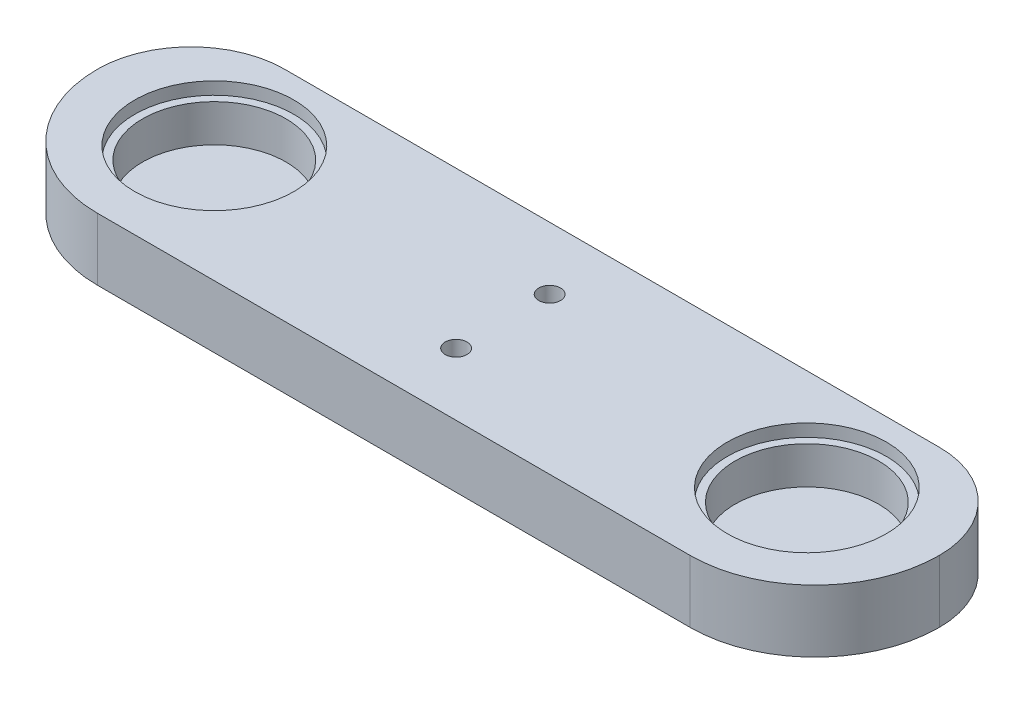
SolidWorks part; units mm, degrees
ref_plane "Front Plane" through (0, 0, 0) normal (0, 0, 1) x (1, 0, 0)
ref_plane "Top Plane" through (0, 0, 0) normal (0, 1, 0) x (1, 0, 0)
ref_plane "Right Plane" through (0, 0, 0) normal (1, 0, 0) x (0, 0, -1)
sketch "Sketch1" plane through (0, 0, 0) normal (0, 1, 0) x (1, 0, 0)
  line L1 (-47.7502, 9.3769) -> (87.2498, 9.3769)
  line L2 (-47.7502, 9.3769) -> (-47.7502, -25.6231)
  line L3 (-47.7502, -25.6231) -> (87.2498, -25.6231)
  line L4 (87.2498, 9.3769) -> (87.2498, -25.6231)
  point P4 (87.2498, 9.3769)
  dimension "D1" = 35
  dimension "D2" = 135
extrude "Boss-Extrude1" add sketch "Sketch1" along normal blind 10
fillet "Fillet1" radius 20 2 edges at (-47.7502, 5, 25.6231) (87.2498, 5, 25.6231)
sketch "Sketch3" plane through (0, 10, 0) normal (0, 1, 0) x (1, 0, 0)
  line L1 (-47.7502, 9.3769) -> (-47.7502, -5.6231) construction
  line L2 (87.2498, 9.3769) -> (-47.7502, 9.3769) construction
  line L3 (19.7498, 5.0244) -> (19.7498, 27.1098) construction
  circle A0 centre (-27.7502, -6.8863) radius 12.75
  circle A1 centre (67.2498, -6.8863) radius 12.75
  dimension "D1" = 25.5
  dimension "D2" = 20
  dimension "D3" = 16.2632
  dimension "D4" = 67.5
extrude "Cut-Extrude1" cut sketch "Sketch3" against normal blind 2
sketch "Sketch4" plane through (0, 8, 0) normal (0, 1, 0) x (1, 0, 0)
  line L0 (19.7498, -1.4238) -> (19.7498, 28.4625) construction
  line L1 (-47.7502, 9.3769) -> (-47.7502, -5.6231) construction
  circle A0 centre (-27.7502, -6.8863) radius 11.5
  circle A1 centre (67.2498, -6.8863) radius 11.5
  dimension "D1" = 23
  dimension "D2" = 67.5
extrude "Cut-Extrude2" cut sketch "Sketch4" against normal blind 6
sketch "Sketch5" plane through (0, 10, 0) normal (0, 1, 0) x (1, 0, 0)
  line L0 (87.2498, -5.6231) -> (87.2498, 9.3769) construction
  line L1 (87.2498, 9.3769) -> (-47.7502, 9.3769) construction
  circle A0 centre (19.7498, -0.6231) radius 1.75
  circle A1 centre (19.7498, -15.6231) radius 1.75
  dimension "D1" = 3.5
  dimension "D2" = 67.5
  dimension "D3" = 10
  dimension "D4" = 15
extrude "Cut-Extrude3" cut sketch "Sketch5" against normal up to next
sketch "Sketch6" plane through (0, 0, 0) normal (0, -1, 0) x (1, 0, 0)
  circle A0 centre (19.7498, 15.6231) radius 3.1
  circle A1 centre (19.7498, 0.6231) radius 3.1
  dimension "D1" = 6.2
  dimension "D2" = 6.2
extrude "Cut-Extrude4" cut sketch "Sketch6" against normal blind 4
fillet "Fillet2" radius 15 2 edges at (-47.7502, 5, -9.3769) (87.2498, 5, -9.3769)
